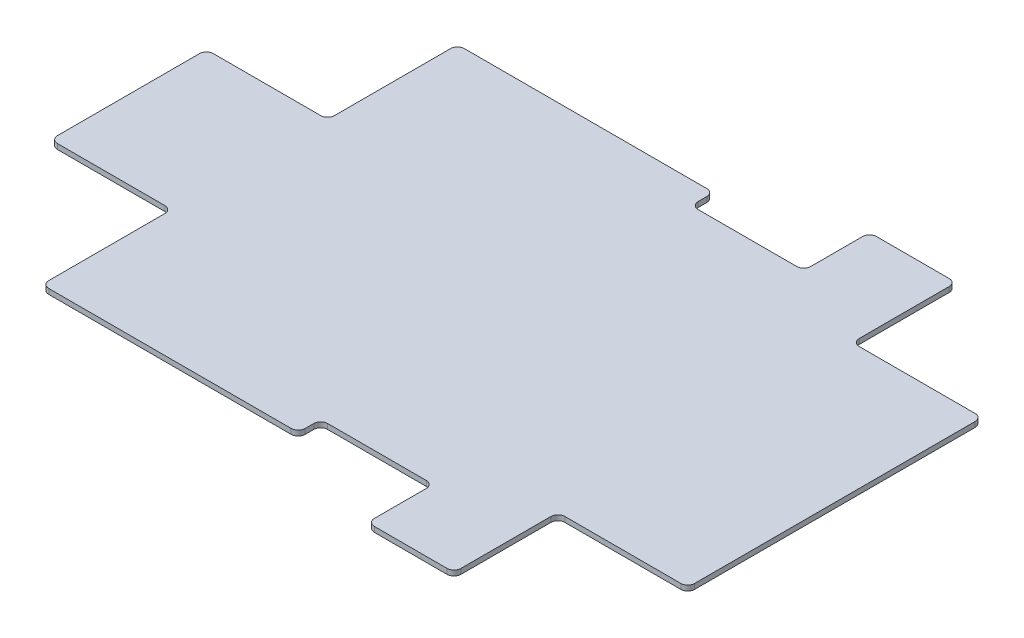
SolidWorks part; units mm, degrees
material "Aleación 1060"
ref_plane "Alzado" through (0, 0, 0) normal (0, 0, 1) x (1, 0, 0)
ref_plane "Planta" through (0, 0, 0) normal (0, 1, 0) x (1, 0, 0)
ref_plane "Vista lateral" through (0, 0, 0) normal (1, 0, 0) x (0, 0, -1)
sketch "Croquis1" plane through (0, 0, 0) normal (0, 1, 0) x (1, 0, 0)
  line L0 (0, 0) -> (-408, 0)
  line L1 (-408, 0) -> (-408, 45)
  line L2 (-408, 45) -> (-338, 45)
  line L3 (-338, 45) -> (-338, 120)
  line L4 (-338, 120) -> (-190, 120)
  line L5 (-190, 120) -> (-190, 107)
  line L6 (-190, 107) -> (-125, 107)
  line L7 (-125, 107) -> (-125, 145)
  line L8 (-125, 145) -> (-75, 145)
  line L9 (-75, 145) -> (-75, 85)
  line L10 (0, 0) -> (0, 85)
  line L11 (0, 85) -> (-75, 85)
  dimension "D1" = 408
  dimension "D2" = 45
  dimension "D3" = 75
  dimension "D4" = 120
  dimension "D5" = 148
  dimension "D6" = 13
  dimension "D7" = 50
  dimension "D8" = 85
  dimension "D9" = 65
  dimension "D10" = 60
extrude "Saliente-Extruir1" add sketch "Croquis1" along normal blind 3
mirror "Simetría1" about plane through (0, 3, 0) normal (0, 0, -1) of "Saliente-Extruir1"
fillet "Redondeo1" radius 4 20 edges at (-408, 1.5, -45) (-338, 1.5, -45) (-338, 1.5, -120) (-190, 1.5, -120) (-190, 1.5, -107) (-125, 1.5, -107) (-125, 1.5, -145) (-75, 1.5, -85) (-75, 1.5, -145) (0, 1.5, -85) (0, 1.5, 85) (-75, 1.5, 85) (-75, 1.5, 145) (-125, 1.5, 145) (-125, 1.5, 107) (-190, 1.5, 107) (-190, 1.5, 120) (-338, 1.5, 120) (-338, 1.5, 45) (-408, 1.5, 45)
sketch "Croquis2" plane through (0, 3, 0) normal (0, 1, 0) x (1, 0, 0)
  line L0 (-408, 0) -> (0, 0) construction
  line L1 (-408, 41) -> (-408, -41) construction
  line L2 (0, -81) -> (0, 81) construction
  line L3 (-214.7209, -131) -> (31.1095, -131) construction
  line L4 (-214.0485, -154) -> (44.3152, -154) construction
  line L5 (-79, -145) -> (-121, -145) construction
  line L6 (-44, -177) -> (-156, -177)
  line L7 (-44, -177) -> (-44, -131)
  line L8 (-44, -131) -> (-156, -131)
  line L9 (-156, -177) -> (-156, -131)
  line L10 (-44, -177) -> (-156, -131) construction
  line L11 (-44, -131) -> (-156, -177) construction
  line L12 (-156, 154) -> (-44, 154) construction
  line L13 (-374, -177) -> (-486, -177)
  line L14 (-374, -177) -> (-374, -131)
  line L15 (-374, -131) -> (-486, -131)
  line L16 (-486, -177) -> (-486, -131)
  line L17 (-374, -177) -> (-486, -131) construction
  line L18 (-374, -131) -> (-486, -177) construction
  line L19 (-44, 177) -> (-156, 177)
  line L20 (-44, 177) -> (-44, 131)
  line L21 (-44, 131) -> (-156, 131)
  line L22 (-156, 177) -> (-156, 131)
  line L23 (-374, 131) -> (-486, 177) construction
  line L24 (-374, 177) -> (-486, 131) construction
  line L25 (-486, 177) -> (-486, 131)
  line L26 (-374, 131) -> (-486, 131)
  line L27 (-374, 177) -> (-374, 131)
  line L28 (-374, 177) -> (-486, 177)
  line L29 (-430, -154) -> (-430, 154) construction
  point P10 (-100, -154)
  point P17 (-100, -145)
  point P20 (-430, -154)
  point P33 (-430, 154)
  dimension "D1" = 131
  dimension "D2" = 154
  dimension "D3" = 46
  dimension "D4" = 112
  dimension "D5" = 330
  dimension "D6" = 308
sketch "Croquis3" plane through (0, 3, 0) normal (0, 1, 0) x (1, 0, 0)
  line L0 (-100, -145) -> (-100, 145) construction
  line L1 (-79, -145) -> (-121, -145) construction
  line L2 (-79, 145) -> (-121, 145) construction
  line L3 (-161.61, 16.8885) -> (-161.61, -25.475) construction
  line L4 (-232.2, 27.5722) -> (-232.2, -25.475) construction
  dimension "D1" = 132.2
  dimension "D2" = 61.61
ref_plane "Plano1" [suppressed] through (-430, 0, 0) normal (1, 0, 0) x (0, 0, -1)
